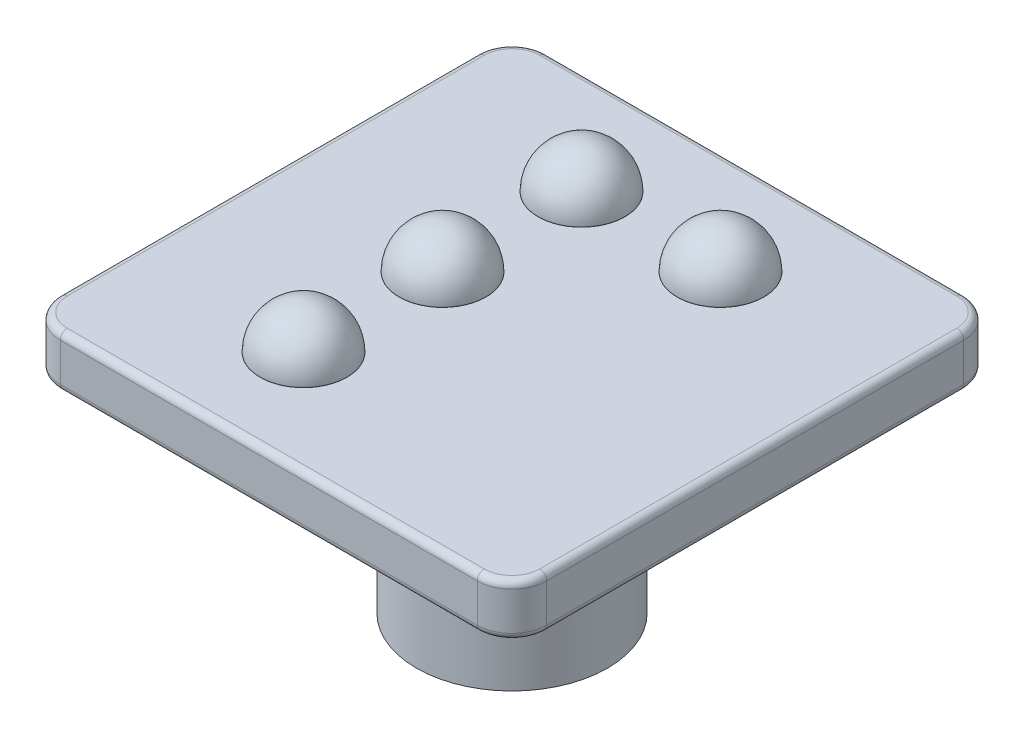
SolidWorks part; units mm, degrees
ref_plane "Front Plane" through (0, 0, 0) normal (0, 0, 1) x (1, 0, 0)
ref_plane "Top Plane" through (0, 0, 0) normal (0, 1, 0) x (1, 0, 0)
ref_plane "Right Plane" through (0, 0, 0) normal (1, 0, 0) x (0, 0, -1)
sketch "Sketch1" plane through (0, 0, 0) normal (0, 1, 0) x (1, 0, 0)
  line L1 (-7.3247, 4.3967) -> (4.6753, 4.3967)
  line L2 (-8.3247, 3.3967) -> (-8.3247, -8.6033)
  line L3 (-7.3247, -9.6033) -> (4.6753, -9.6033)
  line L4 (5.6753, 3.3967) -> (5.6753, -8.6033)
  arc A0 (-8.3247, -8.6033) -> (-7.3247, -9.6033) centre (-7.3247, -8.6033) ccw
  arc A1 (4.6753, -9.6033) -> (5.6753, -8.6033) centre (4.6753, -8.6033) ccw
  arc A2 (4.6753, 4.3967) -> (5.6753, 3.3967) centre (4.6753, 3.3967) cw
  arc A3 (-7.3247, 4.3967) -> (-8.3247, 3.3967) centre (-7.3247, 3.3967) ccw
  point P8 (5.6753, -9.6033)
  point P11 (5.6753, 4.3967)
  point P14 (-8.3247, 4.3967)
  dimension "D3" = 1
  dimension "D1" = 14
  dimension "D2" = 14
extrude "Boss-Extrude1" add sketch "Sketch1" along normal blind 1.5
sketch "Sketch2" plane through (0, 0, 0) normal (0, -1, 0) x (1, 0, 0)
  line L0 (-7.3247, 9.6033) -> (4.6753, 9.6033) construction
  line L1 (5.6753, 8.6033) -> (5.6753, -3.3967) construction
  line L2 (-1.3247, -4.3967) -> (-1.3247, 9.6033) construction
  line L3 (-8.3247, 2.6033) -> (5.6753, 2.6033) construction
  line L4 (-8.3247, -3.3967) -> (-8.3247, 8.6033) construction
  circle A0 centre (-1.3247, 2.6033) radius 2.75
  dimension "D1" = 7
  dimension "D2" = 7
extrude "Boss-Extrude2" add sketch "Sketch2" along normal blind 6
sketch "Sketch3" plane through (0, -6, 0) normal (0, -1, 0) x (1, 0, 0)
  line L0 (-1.3247, 5.3533) -> (-1.3247, -0.1467) construction
  line L1 (-3.3247, 3.1533) -> (0.6753, 3.1533)
  line L2 (-3.3247, 3.1533) -> (-3.3247, 2.0533)
  line L3 (-3.3247, 2.0533) -> (0.6753, 2.0533)
  line L4 (0.6753, 3.1533) -> (0.6753, 2.0533)
  line L5 (-1.8747, 4.6033) -> (-0.7747, 4.6033)
  line L6 (-1.8747, 4.6033) -> (-1.8747, 0.6033)
  line L7 (-1.8747, 0.6033) -> (-0.7747, 0.6033)
  line L8 (-0.7747, 4.6033) -> (-0.7747, 0.6033)
  line L9 (-4.0747, 2.6033) -> (1.4253, 2.6033) construction
  circle A3 centre (-1.3247, 2.6033) radius 2.75 construction
  circle A4 centre (-1.3247, 2.6033) radius 2.75 construction
  dimension "D7" = 0.55
  dimension "D1" = 4
  dimension "D2" = 1.1
  dimension "D3" = 1.1
  dimension "D4" = 4
  dimension "D5" = 2
  dimension "D6" = 2
  dimension "D8" = 0.55
extrude "Cut-Extrude1" cut sketch "Sketch3" against normal blind 6 contours L8 L5 L6 L1 | L1 L8 L3 L4 | L8 L1 L6 L3 | L6 L1 L2 L3 | L8 L3 L6 L7 region at (-2.5997, -6, 2.6033) region at (-1.3247, -6, 3.8783) region at (-1.3247, -6, 2.6033) region at (-0.0497, -6, 2.6033) region at (-1.3247, -6, 1.3283)
chamfer "Chamfer1" distance 0.3 angle 45 12 edges at (-1.3247, -6, 0.6033) (-1.8747, -6, 1.3283) (-2.5997, -6, 2.0533) (-3.3247, -6, 2.6033) (-2.5997, -6, 3.1533) (-0.7747, -6, 1.3283) (-0.0497, -6, 2.0533) (0.6753, -6, 2.6033) (-0.0497, -6, 3.1533) (-0.7747, -6, 3.8783) (-1.3247, -6, 4.6033) (-1.8747, -6, 3.8783)
fillet "Fillet1" radius 1 1 edges at (-1.3247, 0, -0.1467)
sketch "Sketch4" plane through (0, 1.5, 0) normal (0, 1, 0) x (1, 0, 0)
  line L0 (-1.3247, 4.3967) -> (-1.3247, -9.6033) construction
  line L1 (4.6753, 4.3967) -> (-7.3247, 4.3967) construction
  line L2 (-7.3247, -9.6033) -> (4.6753, -9.6033) construction
  line L3 (5.6753, -2.6033) -> (-8.3247, -2.6033) construction
  line L4 (-8.3247, 3.3967) -> (-8.3247, -8.6033) construction
  line L5 (5.6753, -8.6033) -> (5.6753, 3.3967) construction
  line L6 (-3.3247, 4.3967) -> (-3.3247, -9.6033) construction
  line L7 (0.6753, 4.3967) -> (0.6753, -9.6033) construction
  line L8 (-8.3247, 1.3967) -> (5.6753, 1.3967) construction
  line L9 (5.6753, -6.6033) -> (-8.3247, -6.6033) construction
  circle A0 centre (-3.3247, 1.3967) radius 1.25
  circle A2 centre (-3.3247, -2.6033) radius 1.25
  circle A3 centre (-3.3247, -6.6033) radius 1.25
  circle A5 centre (0.6753, 1.3967) radius 1.25
  dimension "D1" = 4
  dimension "D2" = 4
  dimension "D3" = 2
  dimension "D4" = 2
extrude "Boss-Extrude3" add sketch "Sketch4" along normal blind 0.01
dome "Dome1" faces to dome 1 distance 1.25 reverse direction no elliptical dome no face at (-3.3247, 1.51, -0.1467) parameters "D1"=1.25
dome "Dome2" faces to dome 1 distance 1.25 reverse direction no elliptical dome no face at (0.6753, 1.51, -0.1467) parameters "D1"=1.25
dome "Dome3" faces to dome 1 distance 1.25 reverse direction no elliptical dome no face at (-3.3247, 1.51, 3.8533) parameters "D1"=1.25
dome "Dome5" faces to dome 1 distance 1.25 reverse direction no elliptical dome no face at (-3.3247, 1.51, 7.8533) parameters "D1"=1.25
fillet "Fillet3" radius 0.2 16 edges at (5.3824, 1.5, -4.1038) (5.6753, 1.5, 2.6033) (5.3824, 1.5, 9.3104) (-1.3247, 1.5, 9.6033) (-8.0318, 1.5, 9.3104) (-8.0318, 1.5, -4.1038) (-8.3247, 1.5, 2.6033) (-1.3247, 1.5, -4.3967) (5.3824, 0, 9.3104) (5.6753, 0, 2.6033) (5.3824, 0, -4.1038) (-1.3247, 0, -4.3967) (-8.0318, 0, -4.1038) (-8.3247, 0, 2.6033) (-8.0318, 0, 9.3104) (-1.3247, 0, 9.6033)
